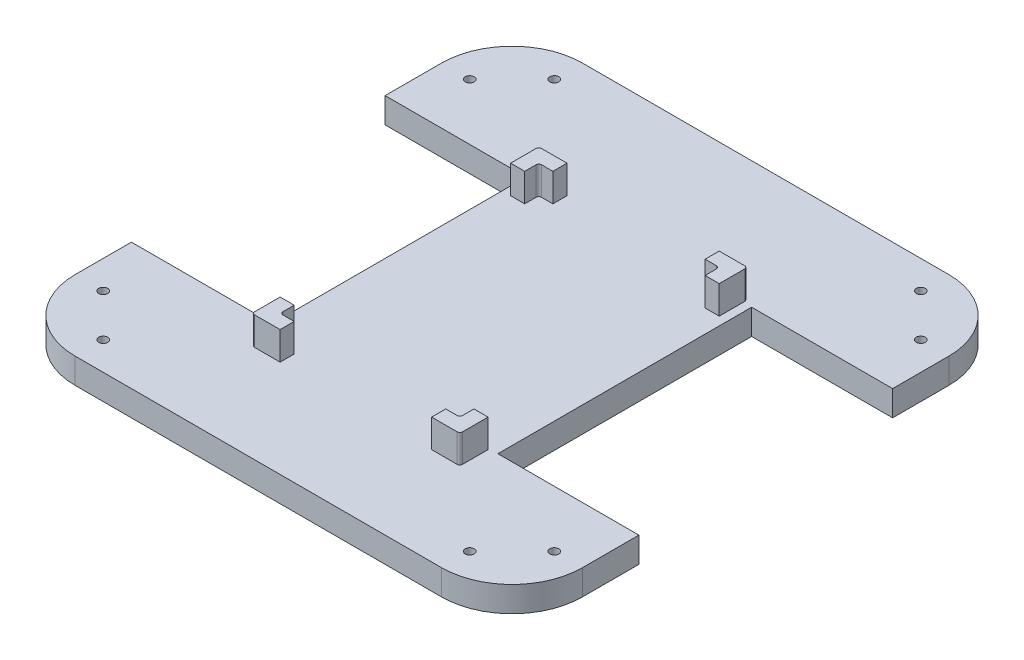
SolidWorks part; units mm, degrees
ref_plane "Front Plane" through (0, 0, 0) normal (0, 0, 1) x (1, 0, 0)
ref_plane "Top Plane" through (0, 0, 0) normal (0, 1, 0) x (1, 0, 0)
ref_plane "Right Plane" through (0, 0, 0) normal (1, 0, 0) x (0, 0, -1)
sketch "Sketch1" plane through (0, 0, 0) normal (0, 1, 0) x (1, 0, 0)
  line L1 (-65, -90) -> (65, -90)
  line L2 (-90, -65) -> (-90, 65)
  line L3 (-65, 90) -> (65, 90)
  line L4 (90, -65) -> (90, 65)
  arc A0 (-90, 65) -> (-65, 90) centre (-65, 65) cw
  arc A1 (65, 90) -> (90, 65) centre (65, 65) cw
  arc A2 (90, -65) -> (65, -90) centre (65, -65) cw
  arc A3 (-65, -90) -> (-90, -65) centre (-65, -65) cw
  point P4 (-90, 0)
  point P6 (0, 90)
  dimension "D3" = 25
  dimension "D1" = 180
  dimension "D2" = 180
extrude "Plate" add sketch "Sketch1" along normal blind 9
sketch "Sketch3" plane through (0, 9, 0) normal (0, 1, 0) x (1, 0, 0)
  line L0 (-65, 90) -> (-65, -90) construction
  line L1 (65, 90) -> (65, -90) construction
  line L2 (-90, 65) -> (90, 65) construction
  line L3 (-90, -65) -> (90, -65) construction
  circle A0 centre (-65, 80) radius 1.6
  circle A1 centre (-80, 65) radius 1.6
  circle A2 centre (80, 65) radius 1.6
  circle A3 centre (80, -65) radius 1.6
  circle A4 centre (65, 80) radius 1.6
  circle A5 centre (65, -80) radius 1.6
  circle A6 centre (-65, -80) radius 1.6
  circle A7 centre (-80, -65) radius 1.6
  dimension "D1" = 3.2
  dimension "D2" = 15
  dimension "D3" = 15
  dimension "D4" = 15
  dimension "D5" = 15
  dimension "D6" = 15
  dimension "D7" = 15
  dimension "D8" = 15
  dimension "D9" = 15
extrude "Hex Holes" cut sketch "Sketch3" against normal through all
sketch "Sketch4" plane through (0, 9, 0) normal (0, 1, 0) x (1, 0, 0)
  line L0 (0, 90) -> (0, -90) construction
  line L1 (-65, 90) -> (65, 90) construction
  line L2 (-65, -90) -> (65, -90) construction
  line L3 (-32, 36.5) -> (-32, 41.5)
  line L4 (-31.5, 41) -> (31.5, 41) construction
  line L5 (-31.5, 41) -> (-31.5, -50) construction
  line L6 (-31.5, -50) -> (31.5, -50) construction
  line L7 (31.5, 41) -> (31.5, -50) construction
  line L8 (-32, 41.5) -> (-27, 41.5)
  line L9 (-27, 41.5) -> (-27, 46.5)
  line L10 (-27, 46.5) -> (-37, 46.5)
  line L11 (-37, 46.5) -> (-37, 36.5)
  line L12 (-37, 36.5) -> (-32, 36.5)
  line L13 (27, 46.5) -> (37, 46.5)
  line L14 (37, 46.5) -> (37, 36.5)
  line L15 (37, 36.5) -> (32, 36.5)
  line L16 (32, 36.5) -> (32, 41.5)
  line L17 (32, 41.5) -> (27, 41.5)
  line L18 (27, 41.5) -> (27, 46.5)
  line L19 (-36.75, -45.5) -> (-36.75, -55.5)
  line L20 (-36.75, -55.5) -> (-26.75, -55.5)
  line L21 (-26.75, -55.5) -> (-26.75, -50.5)
  line L22 (-26.75, -50.5) -> (-31.75, -50.5)
  line L23 (-31.75, -50.5) -> (-31.75, -45.5)
  line L24 (-31.75, -45.5) -> (-36.75, -45.5)
  line L25 (27, -50.5) -> (27, -55.5)
  line L26 (27, -55.5) -> (37, -55.5)
  line L27 (37, -55.5) -> (37, -45.5)
  line L28 (37, -45.5) -> (32, -45.5)
  line L29 (32, -45.5) -> (32, -50.5)
  line L30 (32, -50.5) -> (27, -50.5)
  point P10 (0, 41)
  point P25 (-37, 41.5)
  dimension "D1" = 91
  dimension "D2" = 63
  dimension "D3" = 40
  dimension "D4" = 0.5
  dimension "D5" = 0.5
  dimension "D6" = 5
  dimension "D7" = 0.5
  dimension "D8" = 0.5
  dimension "D9" = 0.5
  dimension "D10" = 0.5
  dimension "D11" = 0.5
extrude "Raspberry Pi Holder" add sketch "Sketch4" along normal blind 10
fillet "Fillet1" radius 1 8 edges at (-37, 14, -46.5) (-32, 14, -41.5) (-31.75, 14, 50.5) (-36.75, 14, 55.5) (32, 14, 50.5) (37, 14, 55.5) (37, 14, -46.5) (32, 14, -41.5)
sketch "Sketch5" plane through (0, 9, 0) normal (0, 1, 0) x (1, 0, 0)
  line L0 (-90, -65) -> (-90, 65) construction
  line L1 (-90, 45) -> (-40, 45)
  line L2 (-90, 45) -> (-90, -45)
  line L3 (-90, -45) -> (-40, -45)
  line L4 (-40, 45) -> (-40, -45)
  line L5 (90, -65) -> (90, 65) construction
  line L6 (90, 45) -> (40, 45)
  line L7 (90, 45) -> (90, -45)
  line L8 (90, -45) -> (40, -45)
  line L9 (40, 45) -> (40, -45)
  point P12 (-90, 0)
  point P14 (90, 0)
  dimension "D1" = 90
  dimension "D2" = 50
extrude "Cut-Extrude1" cut sketch "Sketch5" against normal through all
